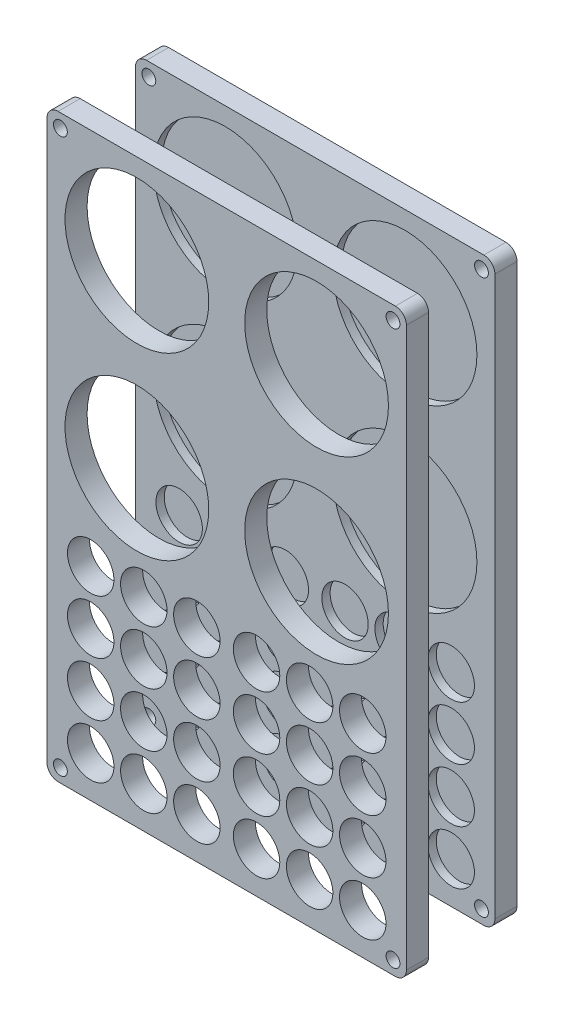
SolidWorks part; units mm, degrees
ref_plane "Front Plane" through (0, 0, 0) normal (1, 0, 0) x (0, 1, 0)
ref_plane "Top Plane" through (0, 0, 0) normal (0, 0, 1) x (0, 1, 0)
ref_plane "Right Plane" through (0, 0, 0) normal (0, 1, 0) x (-1, 0, 0)
sketch "Sketch1" plane through (0, 0, 0) normal (0, 0, 1) x (0, 1, 0)
  line L1 (-105, -65) -> (105, -65)
  line L2 (-105, -65) -> (-105, 65)
  line L3 (-105, 65) -> (105, 65)
  line L4 (105, -65) -> (105, 65)
  line L5 (-105, -65) -> (105, 65) construction
  line L6 (-105, 65) -> (105, -65) construction
  point P0 (0, 0)
  dimension "D1" = 130
  dimension "D2" = 210
extrude "120 x 200 x 67 th" add sketch "Sketch1" along normal blind 40
sketch "Sketch2" plane through (0, 0, 40) normal (0, 0, 1) x (1, 0, 0)
  line L0 (-65, 0) -> (65, 0) construction
  line L1 (-65, 105) -> (-65, -105) construction
  line L2 (65, -105) -> (65, 105) construction
  line L3 (0, 105) -> (0, -105) construction
  line L4 (65, 105) -> (-65, 105) construction
  line L5 (-65, -105) -> (65, -105) construction
  line L6 (-65, 72.5) -> (-58.5, 72.5)
  line L7 (-32.5, 105) -> (-32.5, 98.5)
  line L8 (-6.5, 72.5) -> (0, 72.5)
  line L9 (-65, 40) -> (65, 40) construction
  line L10 (-32.5, 46.5) -> (-32.5, 40)
  line L11 (-62.6582, -100.1582) -> (-65, -100.1582)
  line L12 (-60.1582, -102.6582) -> (-60.1582, -105)
  circle A0 centre (-32.5, 72.5) radius 26
  circle A2 centre (-49.2, -12.1416) radius 8.4 construction
  circle A32 centre (-30, -12.1416) radius 8.4 construction
  circle A33 centre (-10.8, -12.1416) radius 8.4 construction
  circle A34 centre (10.8, -12.1416) radius 8.4 construction
  circle A35 centre (30, -12.1416) radius 8.4 construction
  circle A36 centre (49.2, -12.1416) radius 8.4 construction
  circle A37 centre (10.8, -31.6416) radius 8.4
  circle A38 centre (30, -31.6416) radius 8.4
  circle A39 centre (49.2, -31.6416) radius 8.4
  circle A40 centre (-10.8, -31.6416) radius 8.4
  circle A41 centre (-30, -31.6416) radius 8.4
  circle A42 centre (-49.2, -31.6416) radius 8.4
  circle A43 centre (10.8, -51.1416) radius 8.4
  circle A44 centre (30, -51.1416) radius 8.4
  circle A45 centre (49.2, -51.1416) radius 8.4
  circle A46 centre (-10.8, -51.1416) radius 8.4
  circle A47 centre (-30, -51.1416) radius 8.4
  circle A48 centre (-49.2, -51.1416) radius 8.4
  circle A49 centre (10.8, -70.6416) radius 8.4
  circle A50 centre (30, -70.6416) radius 8.4
  circle A51 centre (49.2, -70.6416) radius 8.4
  circle A52 centre (-10.8, -70.6416) radius 8.4
  circle A53 centre (-30, -70.6416) radius 8.4
  circle A54 centre (-49.2, -70.6416) radius 8.4
  circle A55 centre (10.8, -90.1416) radius 8.4
  circle A56 centre (30, -90.1416) radius 8.4
  circle A57 centre (49.2, -90.1416) radius 8.4
  circle A58 centre (-10.8, -90.1416) radius 8.4
  circle A59 centre (-30, -90.1416) radius 8.4
  circle A60 centre (-49.2, -90.1416) radius 8.4
  circle A61 centre (32.5, 72.5) radius 26
  circle A64 centre (32.5, 7.5) radius 26
  circle A65 centre (-32.5, 7.5) radius 26
  circle A66 centre (-60.1582, -100.1582) radius 2.5
  circle A67 centre (-60.1582, 100.1582) radius 2.5
  circle A68 centre (60.1582, -100.1582) radius 2.5
  circle A69 centre (60.1582, 100.1582) radius 2.5
  point P35 (-32.5, 53)
  dimension "D1" = 52
  dimension "D2" = 3
  dimension "D4" = 5
  dimension "D3" = 5
extrude "16.8 D and 52 D tube holes" cut sketch "Sketch2" against normal blind 35 contours A0 | A61 | A2 | A32 | A33 | A34 | A35 | A36 | A42 | A41 | A40 | A37 | A38 | A39 | A48 | A47 | A46 | A43 | A44 | A45 | A54 | A53 | A52 | A49 | A50 | A51 | A60 | A59 | A58 | A55 | A56 | A57 | A65 | A64 region at (-32.5, 72.5, 40) region at (10.8, -31.6416, 40) region at (30, -31.6416, 40) region at (49.2, -31.6416, 40) region at (-10.8, -31.6416, 40) region at (-30, -31.6416, 40) region at (-49.2, -31.6416, 40) region at (10.8, -51.1416, 40) region at (30, -51.1416, 40) region at (49.2, -51.1416, 40) region at (-10.8, -51.1416, 40) region at (-30, -51.1416, 40) region at (-49.2, -51.1416, 40) region at (10.8, -70.6416, 40) region at (30, -70.6416, 40) region at (49.2, -70.6416, 40) region at (-10.8, -70.6416, 40) region at (-30, -70.6416, 40) region at (-49.2, -70.6416, 40) region at (10.8, -90.1416, 40) region at (30, -90.1416, 40) region at (49.2, -90.1416, 40) region at (-10.8, -90.1416, 40) region at (-30, -90.1416, 40) region at (-49.2, -90.1416, 40) region at (32.5, 72.5, 40) region at (32.5, 7.5, 40) region at (-32.5, 7.5, 40)
fillet "4 mm R filet" radius 4 4 edges at (-65, 105, 20) (65, 105, 20) (-65, -105, 20) (65, -105, 20)
sketch "Sketch3" plane through (0, 0, 0) normal (1, 0, 0) x (0, 1, 0)
  line L0 (-105, 0) -> (-105, 8) construction
  line L1 (-105, 40) -> (-105, 32)
  line L2 (-105, 0) -> (-105, 40) construction
  line L3 (105, 40) -> (105, 0) construction
  line L4 (-105, 8) -> (105, 8)
  line L5 (-105, 8) -> (-105, 32)
  line L6 (-105, 32) -> (105, 32)
  line L7 (105, 8) -> (105, 32)
  line L8 (-105, 8) -> (105, 32) construction
  line L9 (-105, 32) -> (105, 8) construction
  point P11 (0, 20)
  dimension "D1" = 8
  dimension "D2" = 8
extrude "Cut-Extrude1" cut sketch "Sketch3" against normal through all both and the other way through all contours L4 L7 L6 L5 region at (0, 0, 20)
extrude "Cut-Extrude2" cut sketch "Sketch2<3>" against normal through all both and the other way through all contours A66 | A68 | A67 | A69 region at (-60.1582, -100.1582, 40) region at (-60.1582, 100.1582, 40) region at (60.1582, -100.1582, 40) region at (60.1582, 100.1582, 40)
sketch "Sketch2<3>" plane through (0, 0, 40) normal (0, 0, 1) x (1, 0, 0) same geometry as "Sketch2"
